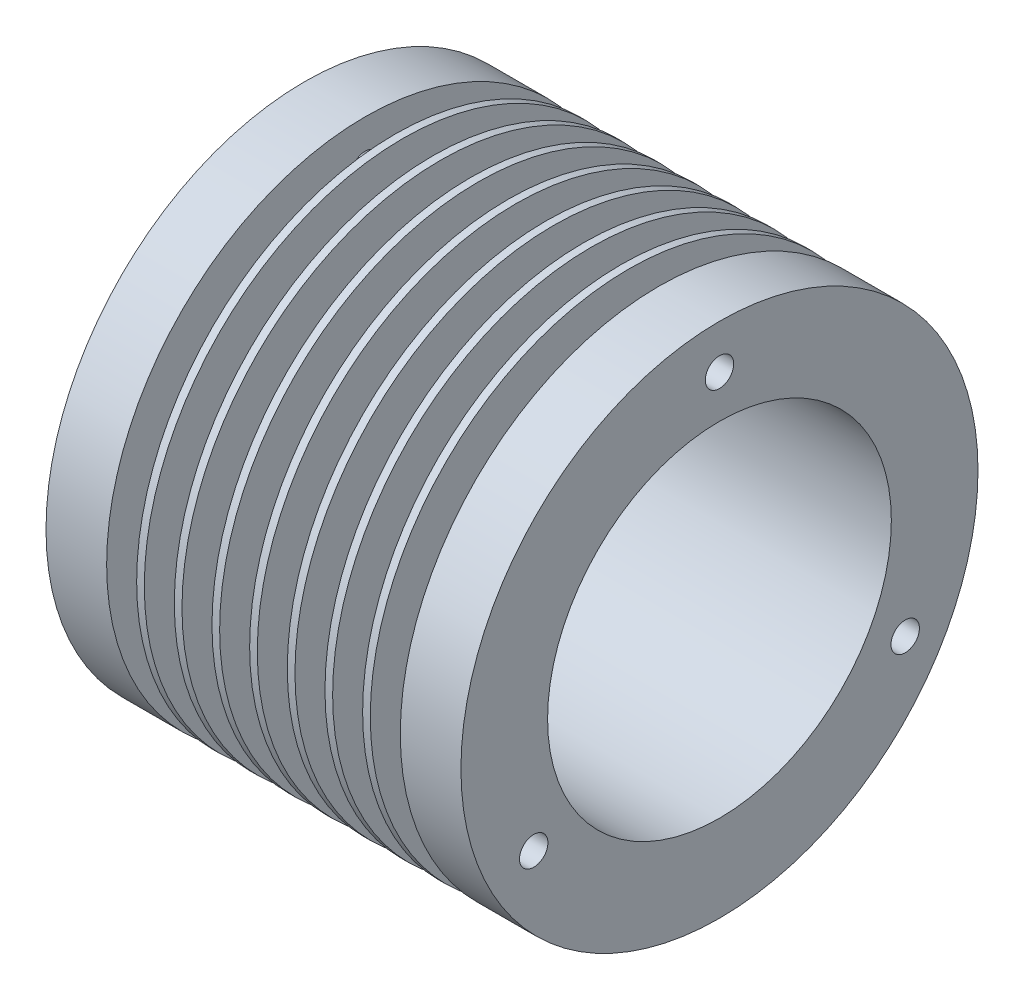
SolidWorks part; units mm, degrees
material "6061-T6 (SS)"
ref_plane "Front Plane" through (0, 0, 0) normal (0, 0, 1) x (1, 0, 0)
ref_plane "Top Plane" through (0, 0, 0) normal (0, 1, 0) x (1, 0, 0)
ref_plane "Right Plane" through (0, 0, 0) normal (1, 0, 0) x (0, 0, -1)
sketch "Sketch1" plane through (0, 0, 0) normal (0, 0, 1) x (1, 0, 0)
  line L0 (4.826, 20.574) -> (4.826, 14.605)
  line L1 (0, 0) -> (33.02, 0)
  line L2 (0, 0) -> (0, 20.574)
  line L3 (0, 20.574) -> (4.826, 20.574)
  line L4 (33.02, 0) -> (33.02, 20.574)
  line L5 (4.826, 14.605) -> (7.2136, 14.605)
  line L6 (7.2136, 14.605) -> (7.2136, 20.574)
  line L7 (7.2136, 20.574) -> (7.8232, 20.574)
  line L8 (7.8232, 20.574) -> (7.8232, 14.605)
  line L9 (7.8232, 14.605) -> (10.2108, 14.605)
  line L10 (10.2108, 14.605) -> (10.2108, 20.574)
  line L11 (10.8204, 20.574) -> (10.8204, 14.605)
  line L12 (10.8204, 14.605) -> (13.208, 14.605)
  line L13 (13.208, 14.605) -> (13.208, 20.574)
  line L14 (13.8176, 20.574) -> (13.8176, 14.605)
  line L15 (13.8176, 14.605) -> (16.2052, 14.605)
  line L16 (16.2052, 14.605) -> (16.2052, 20.574)
  line L17 (16.8148, 20.574) -> (16.8148, 14.605)
  line L18 (16.8148, 14.605) -> (19.2024, 14.605)
  line L19 (19.2024, 14.605) -> (19.2024, 20.574)
  line L20 (19.812, 20.574) -> (19.812, 14.605)
  line L21 (19.812, 14.605) -> (22.1996, 14.605)
  line L22 (22.1996, 14.605) -> (22.1996, 20.574)
  line L23 (22.8092, 20.574) -> (22.8092, 14.605)
  line L24 (22.8092, 14.605) -> (25.1968, 14.605)
  line L25 (25.1968, 14.605) -> (25.1968, 20.574)
  line L26 (25.8064, 20.574) -> (25.8064, 14.605)
  line L27 (25.8064, 14.605) -> (28.194, 14.605)
  line L28 (28.194, 14.605) -> (28.194, 20.574)
  line L29 (10.2108, 20.574) -> (10.8204, 20.574)
  line L30 (13.208, 20.574) -> (13.8176, 20.574)
  line L31 (16.2052, 20.574) -> (16.8148, 20.574)
  line L32 (19.2024, 20.574) -> (19.812, 20.574)
  line L33 (22.1996, 20.574) -> (22.8092, 20.574)
  line L34 (25.1968, 20.574) -> (25.8064, 20.574)
  line L35 (28.194, 20.574) -> (33.02, 20.574)
  dimension "D1" = 2.3876
  dimension "D2" = 5.969
  dimension "D3" = 4.826
  dimension "D4" = 33.02
  dimension "D6" = 0.6096
  dimension "D7" = 20.574
  dimension "D5" = 8
revolve "Revolve1" add sketch "Sketch1" angle 360 about L1
sketch "Sketch2" plane through (0, 0, 0) normal (-1, 0, 0) x (0, 0, 1)
  circle A0 centre (0, 0) radius 13.6779
  circle A1 centre (0, 0) radius 17.0688 construction
  dimension "D1" = 27.3558
  dimension "D2" = 34.1376
extrude "Cut-Extrude1" cut sketch "Sketch2" against normal through all
hole_wizard "#4-40 Tapped Hole2" positions "Sketch5" profile "Sketch6" tap size "#4-40" standard "ANSI Inch" end condition up to next
sketch "Sketch5" plane through (0, 0, 0) normal (-1, 0, 0) x (0, 0, 1)
  circle A0 centre (0, 0) radius 17.0688 construction
  point P0 (0, 17.0688)
sketch "Sketch6" plane through (0, 17.0688, 0) normal (0, 1, 0) x (0, 0, 1)
  line L0 (0, 0) -> (0, 7.8232)
  line L1 (0, 7.8232) -> (1.1303, 7.8232)
  line L2 (1.1303, 7.8232) -> (1.1303, 0)
  line L5 (1.1303, 0) -> (0, 0)
  line L11 (0, -6.35) -> (0, 107.95) construction
  dimension "Thru Tap Drill Dia." = 2.2606
  dimension "Thru Tap Drill Depth" = 7.8232
cosmetic thread "Hole Thread2" parameters "D2"=2.8448
ref_axis "Axis1" through (33.02, 0, 0) along (-1, 0, 0)
pattern_circular "CirPattern1" count 3 every 120 about axis through (33.02, 0, 0) along (-1, 0, 0) of "#4-40 Tapped Hole2"
hole_wizard "#4-40 Tapped Hole3" positions "Sketch7" profile "Sketch8" tap size "#4-40" standard "ANSI Inch" end condition up to next
sketch "Sketch7" plane through (33.02, 0, 0) normal (1, 0, 0) x (0, 0, -1)
  circle A0 centre (0, 0) radius 17.0688 construction
  point P0 (0, 17.0688)
sketch "Sketch8" plane through (33.02, 17.0688, 0) normal (0, 1, 0) x (0, 0, -1)
  line L0 (0, 0) -> (0, 7.8232)
  line L1 (0, 7.8232) -> (1.1303, 7.8232)
  line L2 (1.1303, 7.8232) -> (1.1303, 0)
  line L5 (1.1303, 0) -> (0, 0)
  line L11 (0, -6.35) -> (0, 107.95) construction
  dimension "Thru Tap Drill Dia." = 2.2606
  dimension "Thru Tap Drill Depth" = 7.8232
cosmetic thread "Hole Thread3" parameters "D2"=2.8448
pattern_circular "CirPattern2" count 3 every 120 about axis through (33.02, 0, 0) along (-1, 0, 0) of "#4-40 Tapped Hole3"
